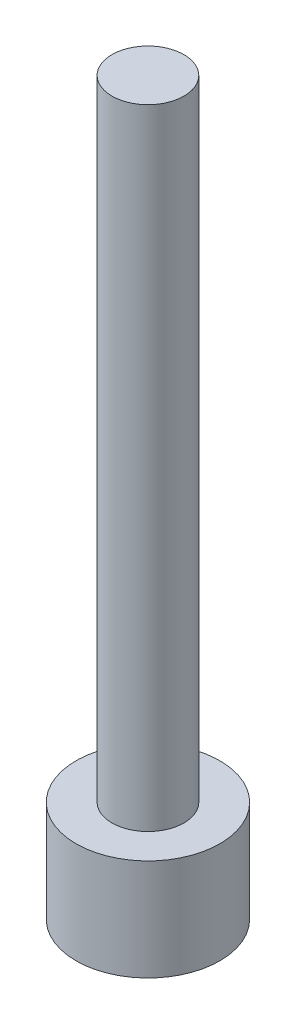
SolidWorks part; units mm, degrees
ref_plane "Спереди" through (0, 0, 0) normal (0, 0, 1) x (1, 0, 0)
ref_plane "Сверху" through (0, 0, 0) normal (0, 1, 0) x (1, 0, 0)
ref_plane "Справа" through (0, 0, 0) normal (1, 0, 0) x (0, 0, -1)
sketch "Эскиз1" plane through (0, 0, 0) normal (1, 0, 0) x (0, 0, -1)
  line L0 (0, 101.7893) -> (0, -44.9948) construction
  line L1 (0, 0) -> (8, 0)
  line L2 (8, 0) -> (8, 11.2811)
  line L3 (8, 11.2811) -> (4, 11.2811)
  line L4 (4, 11.2811) -> (4, 81.3018)
  line L5 (4, 81.3018) -> (0, 81.3018)
  line L7 (0, 81.3018) -> (0, 0)
  point P6 (0, 101.7893)
  point P10 (0, 0)
  point P11 (0, 0)
revolve "Повернуть1" add sketch "Эскиз1" angle 360 about L0
